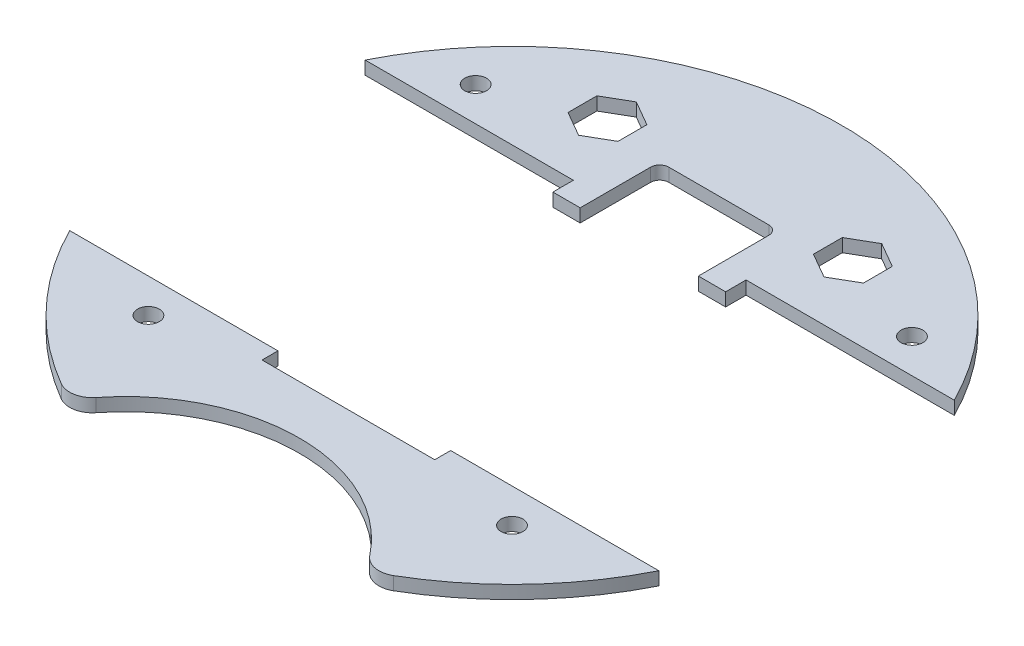
SolidWorks part; units mm, degrees
material "Acrylic (Medium-high impact)"
ref_plane "Front Plane" through (0, 0, 0) normal (0, 0, 1) x (1, 0, 0)
ref_plane "Top Plane" through (0, 0, 0) normal (0, 1, 0) x (1, 0, 0)
ref_plane "Right Plane" through (0, 0, 0) normal (1, 0, 0) x (0, 0, -1)
sketch "Sketch1" plane through (0, 0, 0) normal (0, 1, 0) x (1, 0, 0)
  line L0 (0, -85) -> (-32.4891, -64.8129) construction
  line L1 (0, -85) -> (0, 0) construction
  arc A0 (36.5434, -62.6165) -> (-36.5434, -62.6165) centre (0, 0) ccw
  arc A1 (30.0898, -61.3851) -> (-30.0898, -61.3851) centre (0, -85) ccw
  arc A2 (-30.0898, -61.3851) -> (-36.5434, -62.6165) centre (-34.0231, -58.2982) cw
  arc A3 (36.5434, -62.6165) -> (30.0898, -61.3851) centre (34.0231, -58.2982) cw
  dimension "D1" = 145
  dimension "D2" = 76.5
  dimension "D4" = 5
  dimension "D3" = 85
extrude "Boss-Extrude1" add sketch "Sketch1" along normal blind 2.9
sketch "solenoid placement" plane through (0, 2.9, 0) normal (0, 1, 0) x (1, 0, 0)
  line L4 (-19, -36) -> (19, -36)
  line L5 (-19, 28) -> (-19, -36)
  line L6 (19, 28) -> (-19, 28)
  line L7 (19, -36) -> (19, 28)
  line L8 (-19, -36) -> (19, -36)
  line L9 (-19, 28) -> (-19, -36)
  line L10 (19, 28) -> (-19, 28)
  line L11 (19, -36) -> (19, 28)
  dimension "D1" = 0
extrude "Cut-Extrude1" cut sketch "solenoid placement" against normal through all
sketch "Sketch4" plane through (0, 2.9, 0) normal (0, 1, 0) x (1, 0, 0)
  line L8 (13, 28) -> (13, 43.5)
  line L9 (-13, 28) -> (13, 28)
  line L10 (-13, 43.5) -> (-13, 28)
  line L11 (11, 45.5) -> (-11, 45.5)
  line L28 (13, 28) -> (13, 43.5)
  line L29 (-13, 28) -> (13, 28)
  line L30 (-13, 43.5) -> (-13, 28)
  line L31 (11, 45.5) -> (-11, 45.5)
  arc A4 (-11, 45.5) -> (-13, 43.5) centre (-11, 43.5) ccw
  arc A5 (13, 43.5) -> (11, 45.5) centre (11, 43.5) ccw
  arc A14 (-11, 45.5) -> (-13, 43.5) centre (-11, 43.5) ccw
  arc A15 (13, 43.5) -> (11, 45.5) centre (11, 43.5) ccw
  dimension "D1" = 0
extrude "Cut-Extrude4" cut sketch "Sketch4" against normal through all
sketch "Sketch5" plane through (0, 2.9, 0) normal (0, 1, 0) x (1, 0, 0)
  line L12 (-21.5, 51.1754) -> (-27, 54.3509)
  line L13 (-27, 54.3509) -> (-32.5, 51.1754)
  line L14 (-32.5, 51.1754) -> (-32.5, 44.8246)
  line L15 (-32.5, 44.8246) -> (-27, 41.6491)
  line L16 (-27, 41.6491) -> (-21.5, 44.8246)
  line L17 (-21.5, 44.8246) -> (-21.5, 51.1754)
  line L18 (-21.5, 51.1754) -> (-27, 54.3509)
  line L19 (-27, 54.3509) -> (-32.5, 51.1754)
  line L20 (-32.5, 51.1754) -> (-32.5, 44.8246)
  line L21 (-32.5, 44.8246) -> (-27, 41.6491)
  line L22 (-27, 41.6491) -> (-21.5, 44.8246)
  line L23 (-21.5, 44.8246) -> (-21.5, 51.1754)
  line L24 (21.5, 51.1754) -> (21.5, 44.8246)
  line L25 (21.5, 44.8246) -> (27, 41.6491)
  line L26 (27, 41.6491) -> (32.5, 44.8246)
  line L27 (32.5, 44.8246) -> (32.5, 51.1754)
  line L28 (32.5, 51.1754) -> (27, 54.3509)
  line L29 (27, 54.3509) -> (21.5, 51.1754)
  line L42 (21.5, 51.1754) -> (21.5, 44.8246)
  line L43 (21.5, 44.8246) -> (27, 41.6491)
  line L44 (27, 41.6491) -> (32.5, 44.8246)
  line L45 (32.5, 44.8246) -> (32.5, 51.1754)
  line L46 (32.5, 51.1754) -> (27, 54.3509)
  line L47 (27, 54.3509) -> (21.5, 51.1754)
  dimension "D1" = 0
  dimension "D2" = 0
extrude "Cut-Extrude5" cut sketch "Sketch5" against normal through all
sketch "Sketch6" plane through (0, 2.9, 0) normal (0, 1, 0) x (1, 0, 0)
  circle A1 centre (40, -40) radius 2.4
  circle A2 centre (40, -40) radius 2.4
  circle A3 centre (-40, -40) radius 2.4
  circle A4 centre (-40, -40) radius 2.4
  circle A5 centre (48, 40) radius 2.4
  circle A6 centre (48, 40) radius 2.4
  circle A7 centre (-48, 40) radius 2.4
  circle A8 centre (-48, 40) radius 2.4
  dimension "D1" = 0
  dimension "D2" = 0
  dimension "D3" = 0
  dimension "D4" = 0
extrude "Cut-Extrude6" cut sketch "Sketch6" against normal through all
sketch "Sketch3" plane through (0, 2.9, 0) normal (0, 1, 0) x (1, 0, 0)
  line L0 (-19, 28) -> (-19, 32.5)
  line L1 (72.5, -32.5) -> (-72.5, -32.5)
  line L2 (72.5, -32.5) -> (72.5, 32.5)
  line L3 (72.5, 32.5) -> (19, 32.5)
  line L4 (-72.5, -32.5) -> (-72.5, 32.5)
  line L5 (72.5, -32.5) -> (-72.5, 32.5) construction
  line L6 (72.5, 32.5) -> (-72.5, -32.5) construction
  line L7 (-19, 28) -> (19, 28)
  line L8 (19, 28) -> (19, 32.5)
  line L9 (-19, 32.5) -> (-72.5, 32.5)
  line L10 (-19, 28) -> (-19, -36) construction
  line L11 (-13, 28) -> (-19, 28) construction
  arc A0 (36.5434, -62.6165) -> (-36.5434, -62.6165) centre (0, 0) ccw construction
  point P0 (0, 0)
  dimension "D1" = 65
extrude "Cut-Extrude3" cut sketch "Sketch3" against normal through all
equation "\"smallPulleyTeeth\"= 15"
equation "\"largePulleyTeeth\"= 30"
equation "\"eighthThick\"= 2.9mm"
equation "\"sixteenthThick\" = 1.7mm"
equation "\"quarterThick\"=6.0mm"
equation "\"OD\" = 145mm"
equation "\"puckAngle\" = 60.5deg"
equation "\"D1@Sketch1\"=\"OD\""
equation "\"puckDiam\" = 76.5mm"
equation "\"D2@Sketch1\"=\"puckDiam\""
equation "\"D1@Boss-Extrude1\"=\"eighthThick\""
equation "\"axlePress\" = 5.9mm"
equation "\"press\" = 0.2mm"
equation "\"wheelClear\" = 0.3mm"
equation "\"10-32clear\" = 4.8mm"
equation "\"6-32clear\" = 3.3mm"
equation "\"8-32clear\" = 4.0mm"
equation "\"wheelHeight\" = 22mm"
equation "\"wheelWell\" = 65mm"
equation "\"D1@Sketch3\"=\"wheelWell\""
equation "\"puckDist\" = 85mm"
equation "\"scoopFillet\" = 5mm"
equation "\"4-40clear\" = 3.0mm"
equation "\"D3@Sketch1\"=\"puckDist\""
equation "\"D4@Sketch1\"=\"scoopFillet\""
